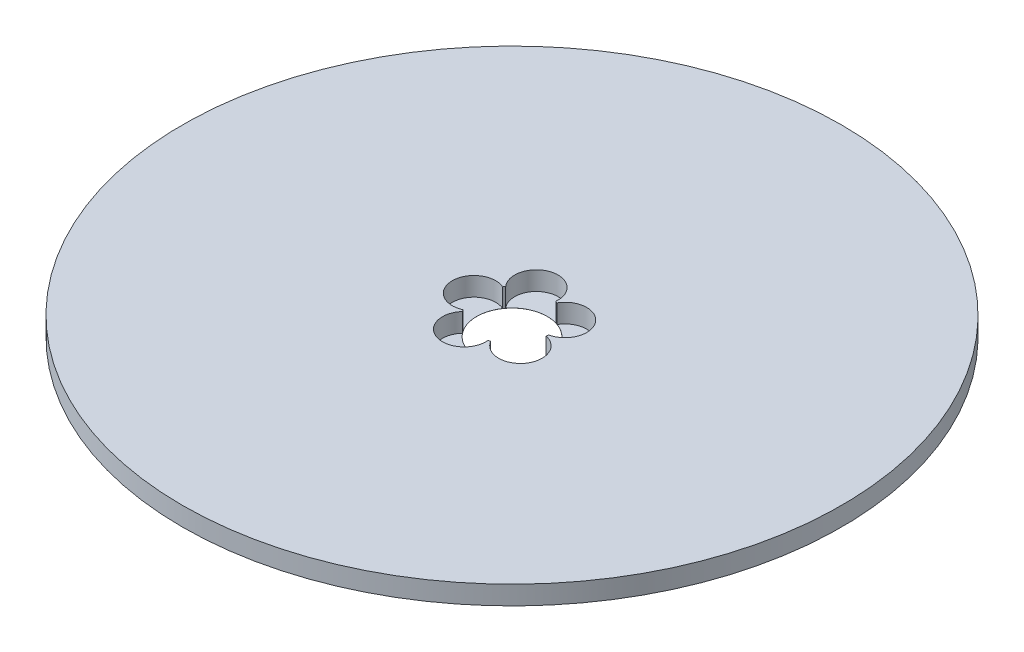
SolidWorks part; units mm, degrees
ref_plane "Front Plane" through (0, 0, 0) normal (0, 0, 1) x (1, 0, 0)
ref_plane "Top Plane" through (0, 0, 0) normal (0, 1, 0) x (1, 0, 0)
ref_plane "Right Plane" through (0, 0, 0) normal (1, 0, 0) x (0, 0, -1)
sketch "Sketch1" plane through (0, 0, 0) normal (0, 1, 0) x (1, 0, 0)
  circle A0 centre (0, 0) radius 70
  dimension "FLANGE_OD" = 140
extrude "Boss-Extrude1" add sketch "Sketch1" along normal blind 4
sketch "Sketch2" plane through (0, 0, 0) normal (0, 1, 0) x (1, 0, 0)
  circle A0 centre (0, 0) radius 7.5
  dimension "BORE_D" = 15
extrude "Cut-Extrude1" cut sketch "Sketch2" along normal through all
sketch "Sketch3" plane through (0, 4, 0) normal (0, 1, 0) x (1, 0, 0)
  circle A0 centre (0, 0) radius 8.0682 construction
  circle A1 centre (-8.0682, 0) radius 4.6115
  dimension "BOLT_D" = 9.223
  dimension "BOLT_PCD" = 16.1364
extrude "Cut-Extrude2" cut sketch "Sketch3" against normal blind 3.9912
pattern_circular "CirPattern1" count 5 over 360 about axis through (0, 0, 0) along (0, 1, 0) of "Cut-Extrude2"
